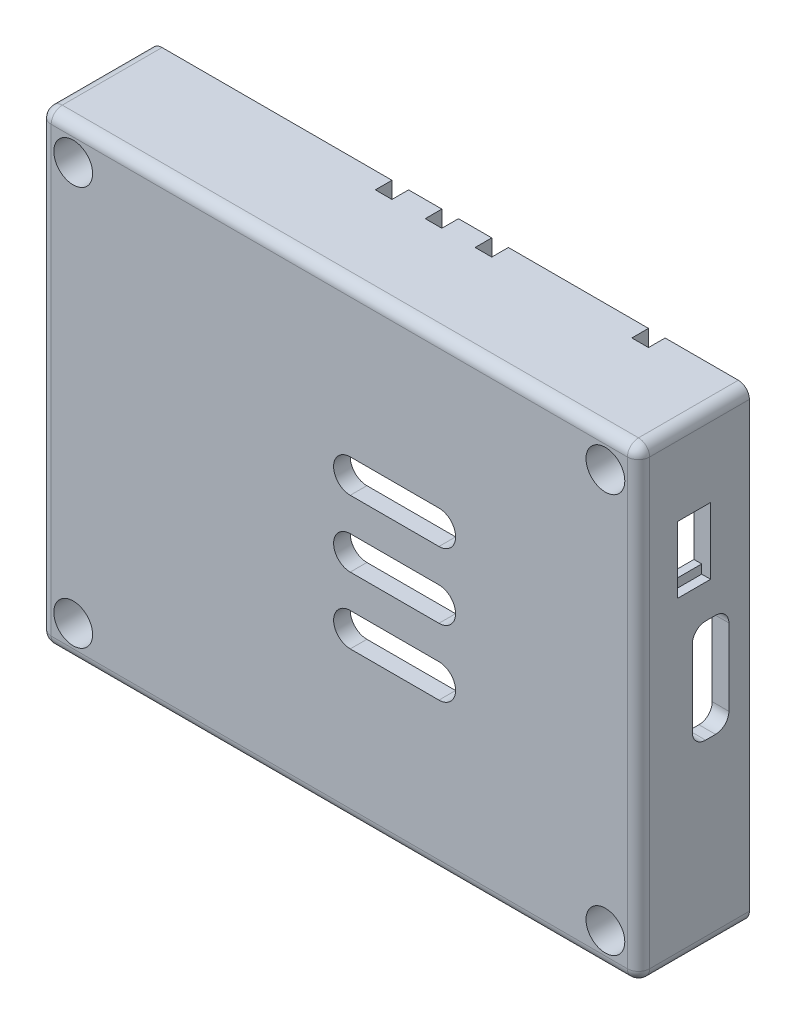
SolidWorks part; units mm, degrees
ref_plane "前视基准面" through (0, 0, 0) normal (0, 0, 1) x (1, 0, 0)
ref_plane "上视基准面" through (0, 0, 0) normal (0, 1, 0) x (1, 0, 0)
ref_plane "右视基准面" through (0, 0, 0) normal (1, 0, 0) x (0, 0, -1)
other "Configuration Table"
sketch "草图2" plane through (0, 0, 0) normal (0, 0, 1) x (1, 0, 0)
  line L32 (0.7633, 42.7757) -> (0.7633, 44.263) construction
  line L33 (0.7633, 44.263) -> (-41.2112, 44.263) construction
  line L34 (-41.2112, 44.263) -> (-41.2112, 42.7757) construction
  line L35 (-44.2239, 39.763) -> (-45.7112, 39.763) construction
  line L36 (-45.7112, 39.763) -> (-45.7112, 9.7885) construction
  line L37 (-45.7112, 9.7885) -> (-44.2239, 9.7885) construction
  line L38 (-41.2112, 6.7758) -> (-41.2112, 5.2885) construction
  line L39 (-41.2112, 5.2885) -> (0.7633, 5.2885) construction
  line L40 (0.7633, 5.2885) -> (0.7633, 6.7758) construction
  line L41 (3.776, 9.7885) -> (5.2633, 9.7885) construction
  line L42 (5.2633, 9.7885) -> (5.2633, 20.2756) construction
  line L43 (5.2633, 20.2756) -> (-0.4009, 20.283) construction
  line L44 (-0.4136, 20.2957) -> (-0.4136, 29.2557) construction
  line L45 (-0.4009, 29.2684) -> (5.2633, 29.2684) construction
  line L46 (5.2633, 29.2684) -> (5.2633, 39.763) construction
  line L47 (5.2633, 39.763) -> (3.776, 39.763) construction
  circle A1 centre (-4.0239, 32.2757) radius 1.125 construction
  arc A12 (0.7633, 42.7757) -> (3.776, 39.763) centre (3.776, 42.7757) ccw construction
  arc A13 (-44.2239, 39.763) -> (-41.2112, 42.7757) centre (-44.2239, 42.7757) ccw construction
  arc A14 (-41.2112, 6.7758) -> (-44.2239, 9.7885) centre (-44.2239, 6.7758) ccw construction
  arc A15 (3.776, 9.7885) -> (0.7633, 6.7758) centre (3.776, 6.7758) ccw construction
  arc A16 (-0.4136, 20.2957) -> (-0.4009, 20.283) centre (-0.4009, 20.2957) ccw construction
  arc A17 (-0.4009, 29.2684) -> (-0.4136, 29.2557) centre (-0.4009, 29.2557) ccw construction
sketch "草图3" plane through (0, 0, 0) normal (0, 0, 1) x (1, 0, 0)
  line L1 (-47.2112, 45.763) -> (6.7633, 45.763)
  line L2 (-47.2112, 45.763) -> (-47.2112, 3.7885)
  line L3 (-47.2112, 3.7885) -> (6.7633, 3.7885)
  line L4 (6.7633, 45.763) -> (6.7633, 3.7885)
  line L6 (-45.7112, 39.763) -> (-45.7112, 9.7885) construction
  line L7 (0.7633, 44.263) -> (-41.2112, 44.263) construction
  point P4 (-20.2239, 45.763)
  point P7 (-20.2239, 44.263)
  point P11 (-47.2112, 24.7757)
  point P12 (-45.7112, 24.7757)
  dimension "D1" = 1.5
  dimension "D2" = 1.5
extrude "凸台-拉伸1" add sketch "草图3" along normal blind 10
sketch "草图4" plane through (0, 0, 0) normal (0, 0, 1) x (1, 0, 0)
  line L32 (0.7633, 42.7757) -> (0.7633, 44.263)
  line L33 (0.7633, 44.263) -> (-41.2112, 44.263)
  line L34 (-41.2112, 44.263) -> (-41.2112, 42.7757)
  line L35 (-44.2239, 39.763) -> (-45.7112, 39.763)
  line L36 (-45.7112, 39.763) -> (-45.7112, 9.7885)
  line L37 (-45.7112, 9.7885) -> (-44.2239, 9.7885)
  line L38 (-41.2112, 6.7758) -> (-41.2112, 5.2885)
  line L39 (-41.2112, 5.2885) -> (0.7633, 5.2885)
  line L40 (0.7633, 5.2885) -> (0.7633, 6.7758)
  line L41 (3.776, 9.7885) -> (5.2633, 9.7885)
  line L46 (5.2633, 9.7885) -> (5.2633, 39.763)
  line L47 (5.2633, 39.763) -> (3.776, 39.763)
  arc A12 (0.7633, 42.7757) -> (3.776, 39.763) centre (3.776, 42.7757) ccw
  arc A13 (-44.2239, 39.763) -> (-41.2112, 42.7757) centre (-44.2239, 42.7757) ccw
  arc A14 (-41.2112, 6.7758) -> (-44.2239, 9.7885) centre (-44.2239, 6.7758) ccw
  arc A15 (3.776, 9.7885) -> (0.7633, 6.7758) centre (3.776, 6.7758) ccw
  point P9 (5.2633, 20.0021)
  point P12 (5.5493, 9.7885)
  point P18 (0, 0)
extrude "切除-拉伸1" cut sketch "草图4" along normal blind 8.5
sketch "草图5" plane through (0, 0, 8.5) normal (0, 0, -1) x (-1, 0, 0)
  line L0 (45.7112, 39.763) -> (45.7112, 9.7885) construction
  line L1 (-6.7633, 3.7885) -> (-6.7633, 45.763) construction
  line L6 (15.2367, 20.2757) -> (15.2367, 29.2757) construction
  line L7 (6.7367, 20.2757) -> (6.7367, 29.2757)
  line L8 (23.7367, 20.2757) -> (23.7367, 29.2757)
  line L9 (15.2367, 20.2757) -> (15.2367, 29.2757) construction
  line L10 (7.4867, 20.2757) -> (7.4867, 29.2757)
  line L11 (22.9867, 20.2757) -> (22.9867, 29.2757)
  arc A0 (6.7367, 20.2757) -> (23.7367, 20.2757) centre (15.2367, 20.2757) ccw
  arc A1 (23.7367, 29.2757) -> (6.7367, 29.2757) centre (15.2367, 29.2757) ccw
  arc A2 (7.4867, 20.2757) -> (22.9867, 20.2757) centre (15.2367, 20.2757) ccw
  arc A3 (22.9867, 29.2757) -> (7.4867, 29.2757) centre (15.2367, 29.2757) ccw
  point P0 (0, 0)
  point P3 (45.7112, 24.7757)
  point P14 (15.2367, 24.7757)
  point P19 (15.2367, 11.7757)
  point P20 (15.2367, 37.7757)
  point P23 (15.2367, 24.7757)
  point P28 (15.2367, 12.5257)
  point P29 (15.2367, 37.0257)
  dimension "D1" = 17
  dimension "D2" = 26
  dimension "D3" = 24.5
  dimension "D4" = 15.5
  dimension "D5" = 22
extrude "凸台-拉伸2" add sketch "草图5" along normal blind 1
sketch "草图6" plane through (0, 0, 7.5) normal (0, 0, -1) x (-1, 0, 0)
  line L1 (6.7367, 28.7757) -> (12.7367, 28.7757)
  line L2 (6.7367, 28.7757) -> (6.7367, 20.7757)
  line L3 (6.7367, 20.7757) -> (12.7367, 20.7757)
  line L4 (23.7367, 28.7757) -> (23.7367, 20.7757)
  line L11 (6.7367, 29.2757) -> (6.7367, 20.2757) construction
  line L12 (23.7367, 20.2757) -> (23.7367, 29.2757) construction
  line L13 (7.4867, 29.2757) -> (7.4867, 20.2757) construction
  line L14 (15.2367, 28.7757) -> (15.2367, 20.7757) construction
  line L15 (17.7367, 39.4071) -> (12.7367, 39.4071)
  line L16 (17.7367, 39.4071) -> (17.7367, 28.7757)
  line L17 (17.7367, 10.1444) -> (12.7367, 10.1444)
  line L18 (12.7367, 39.4071) -> (12.7367, 28.7757)
  line L19 (12.7367, 20.7757) -> (12.7367, 10.1444)
  line L20 (17.7367, 28.7757) -> (23.7367, 28.7757)
  line L21 (17.7367, 20.7757) -> (17.7367, 10.1444)
  line L22 (17.7367, 20.7757) -> (23.7367, 20.7757)
  point P8 (7.4867, 24.7757)
  point P9 (23.7367, 24.7757)
  point P21 (15.2367, 39.4071)
  dimension "D1" = 8
  dimension "D2" = 5
extrude "切除-拉伸6" cut sketch "草图6" against normal up to surface (1 mm away) up to face at (-15.2367, 24.7757, 8.5)
sketch "草图7" plane through (0, 0, 8.5) normal (0, 0, -1) x (-1, 0, 0)
  line L0 (45.7112, 39.763) -> (45.7112, 9.7885) construction
  line L2 (12.7367, 36.6114) -> (17.7367, 12.94) construction
  line L3 (11.2367, 24.7757) -> (19.2367, 24.7757) construction
  line L4 (11.2367, 26.2757) -> (19.2367, 26.2757)
  line L5 (11.2367, 23.2757) -> (19.2367, 23.2757)
  line L6 (11.2367, 18.7757) -> (19.2367, 18.7757) construction
  line L7 (11.2367, 20.2757) -> (19.2367, 20.2757)
  line L8 (11.2367, 17.2757) -> (19.2367, 17.2757)
  line L10 (15.2367, 24.7757) -> (15.2367, 36.6114) construction
  line L13 (17.7367, 36.6114) -> (12.7367, 12.94) construction
  line L14 (6.7535, 24.7757) -> (27.8266, 24.7757) construction
  line L15 (11.2367, 30.7757) -> (19.2367, 30.7757) construction
  line L16 (11.2367, 29.2757) -> (19.2367, 29.2757)
  line L17 (11.2367, 32.2757) -> (19.2367, 32.2757)
  arc A0 (11.2367, 26.2757) -> (11.2367, 23.2757) centre (11.2367, 24.7757) ccw
  arc A1 (19.2367, 23.2757) -> (19.2367, 26.2757) centre (19.2367, 24.7757) ccw
  arc A2 (11.2367, 20.2757) -> (11.2367, 17.2757) centre (11.2367, 18.7757) ccw
  arc A3 (19.2367, 17.2757) -> (19.2367, 20.2757) centre (19.2367, 18.7757) ccw
  arc A6 (11.2367, 29.2757) -> (11.2367, 32.2757) centre (11.2367, 30.7757) cw
  arc A7 (19.2367, 32.2757) -> (19.2367, 29.2757) centre (19.2367, 30.7757) cw
  point P3 (45.7112, 24.7757)
  point P8 (15.2367, 24.7757)
  point P14 (15.2367, 18.7757)
  point P27 (15.2367, 30.7757)
  dimension "D1" = 8
  dimension "D2" = 1.5
  dimension "D3" = 6
extrude "切除-拉伸7" cut sketch "草图7" against normal up to surface (1.5 mm away) up to face at (-20.2239, 24.7757, 10)
sketch "草图8" plane through (0, 0, 8.5) normal (0, 0, -1) x (-1, 0, 0)
  line L0 (-5.2633, 9.7885) -> (-5.2633, 20.2756) construction
  line L1 (-3.776, 9.7885) -> (-5.2633, 9.7885)
  line L2 (-3.776, 9.7885) -> (-3.776, 11.7885)
  line L3 (-3.776, 11.7885) -> (-5.2633, 11.7885)
  line L4 (-5.2633, 9.7885) -> (-5.2633, 11.7885)
  line L5 (45.7112, 39.763) -> (45.7112, 9.7885) construction
  line L6 (44.2239, 9.7885) -> (45.7112, 9.7885)
  line L7 (44.2239, 9.7885) -> (44.2239, 11.7885)
  line L8 (44.2239, 11.7885) -> (45.7112, 11.7885)
  line L9 (45.7112, 9.7885) -> (45.7112, 11.7885)
  line L11 (44.2239, 39.763) -> (45.7112, 39.763)
  line L12 (44.2239, 39.763) -> (44.2239, 37.763)
  line L13 (44.2239, 37.763) -> (45.7112, 37.763)
  line L14 (45.7112, 39.763) -> (45.7112, 37.763)
  circle A0 centre (4.0239, 32.2757) radius 0.625
  circle A1 centre (4.0239, 32.2757) radius 2.25
  dimension "D1" = 1.25
  dimension "D2" = 4.5
  dimension "D3" = 2
  dimension "D4" = 2
  dimension "D5" = 2
extrude "凸台-拉伸3" add sketch "草图8" along normal blind 5
sketch "草图9" plane through (0, 0, 10) normal (0, 0, 1) x (1, 0, 0)
  line L0 (-20.2239, 45.763) -> (-20.2239, 3.7885) construction
  line L1 (6.7633, 45.763) -> (-47.2112, 45.763) construction
  line L2 (-47.2112, 3.7885) -> (6.7633, 3.7885) construction
  line L4 (-47.2112, 45.763) -> (-47.2112, 3.7885) construction
  line L5 (-47.2112, 24.7757) -> (6.7633, 24.7757) construction
  line L6 (6.7633, 3.7885) -> (6.7633, 45.763) construction
  circle A4 centre (-44.2239, 42.7757) radius 0.9
  circle A5 centre (3.776, 42.7757) radius 0.9
  circle A6 centre (3.776, 6.7758) radius 0.9
  circle A7 centre (-44.2239, 6.7758) radius 0.9
  dimension "D1" = 1.8
extrude "切除-拉伸8" cut sketch "草图9" against normal through all
sketch "草图10" plane through (0, 0, 10) normal (0, 0, 1) x (1, 0, 0)
  circle A0 centre (-44.2239, 42.7757) radius 1.75
  circle A1 centre (3.776, 42.7757) radius 1.75
  circle A2 centre (3.776, 6.7758) radius 1.75
  circle A3 centre (-44.2239, 6.7758) radius 1.75
  dimension "D1" = 3.5
  dimension "D2" = 3.5
  dimension "D3" = 3.5
  dimension "D4" = 3.5
extrude "切除-拉伸9" cut sketch "草图10" against normal offset from surface (8.8 mm away) 1.2 up to face at (-45.1239, 6.7758, 0)
sketch "草图11" plane through (0, 0, 0) normal (0, 0, -1) x (-1, 0, 0)
  line L0 (-0.7633, 44.263) -> (41.2112, 44.263) construction
  line L1 (0.8367, 44.263) -> (2.3367, 44.263)
  line L2 (0.8367, 44.263) -> (0.8367, 45.763)
  line L3 (0.8367, 45.763) -> (2.3367, 45.763)
  line L4 (2.3367, 44.263) -> (2.3367, 45.763)
  line L5 (-6.7633, 45.763) -> (47.2112, 45.763) construction
  line L6 (-6.7633, 3.7885) -> (-6.7633, 45.763) construction
  dimension "D1" = 1.5
  dimension "D2" = 7.6
extrude "切除-拉伸10" cut sketch "草图11" against normal blind 1.5
sketch "草图12" plane through (0, 0, 0) normal (0, 0, -1) x (-1, 0, 0)
  line L5 (-6.7633, 3.7885) -> (-6.7633, 45.763) construction
  line L8 (-6.7633, 29.2757) -> (-5.2633, 29.2757)
  line L9 (-6.7633, 29.2757) -> (-6.7633, 20.2757)
  line L10 (-6.7633, 20.2757) -> (-5.2633, 20.2757)
  line L11 (-5.2633, 29.2757) -> (-5.2633, 20.2757)
  line L12 (-5.2633, 9.7885) -> (-5.2633, 20.2756) construction
  line L13 (47.2112, 45.763) -> (47.2112, 3.7885) construction
  point P10 (47.2112, 24.7757)
  point P11 (-6.7633, 24.7757)
  dimension "D1" = 9
sketch "草图13" plane through (6.7633, 0, 0) normal (1, 0, 0) x (0, 0, -1)
  line L0 (-10, 3.7885) -> (-10, 45.763) construction
  line L1 (-5.15, 29.4257) -> (-1.85, 29.4257)
  line L2 (-5.15, 29.4257) -> (-5.15, 20.1257)
  line L3 (-5.15, 20.1257) -> (-1.85, 20.1257)
  line L4 (-1.85, 29.4257) -> (-1.85, 20.1257)
  line L5 (0, 39.763) -> (0, 9.7885) construction
  point P6 (-10, 24.7757)
  point P7 (-1.85, 24.7757)
  dimension "D1" = 5.15
  dimension "D2" = 3.3
  dimension "D3" = 9.3
extrude "切除-拉伸16" cut sketch "草图13" against normal up to surface (1.5 mm away) up to face at (5.2633, 20.4466, 4)
fillet "圆角2" radius 1.2 4 edges at (6.0133, 20.1257, 5.15) (6.0133, 29.4257, 1.85) (6.0133, 29.4257, 5.15) (6.0133, 20.1257, 1.85)
sketch "草图14" plane through (0, 0, 0) normal (0, 0, -1) x (-1, 0, 0)
  line L0 (45.7112, 39.763) -> (45.7112, 9.7885) construction
  line L1 (45.7112, 19.7757) -> (47.2112, 19.7757)
  line L2 (45.7112, 19.7757) -> (45.7112, 29.7757)
  line L3 (45.7112, 29.7757) -> (47.2112, 29.7757)
  line L4 (47.2112, 19.7757) -> (47.2112, 29.7757)
  line L5 (47.2112, 45.763) -> (47.2112, 3.7885) construction
  point P8 (47.2112, 24.7757)
  point P9 (47.2112, 24.7757)
  dimension "D1" = 10
extrude "切除-拉伸17" cut sketch "草图14" against normal blind 1.8
sketch "草图15" plane through (6.7633, 0, 0) normal (1, 0, 0) x (0, 0, -1)
  line L0 (0, 42.7757) -> (0, 39.763) construction
  line L1 (-6.5, 38.463) -> (-3.5, 38.463)
  line L2 (-6.5, 38.463) -> (-6.5, 32.463)
  line L3 (-6.5, 32.463) -> (-3.5, 32.463)
  line L4 (-3.5, 38.463) -> (-3.5, 32.463)
  line L5 (-6.5, 35.463) -> (-3.5, 35.463) construction
  line L6 (-10, 45.763) -> (0, 45.763) construction
  dimension "D1" = 3
  dimension "D2" = 6
  dimension "D3" = 6.5
  dimension "D4" = 10.3
extrude "切除-拉伸18" cut sketch "草图15" against normal blind 0.8
sketch "草图16" plane through (5.9633, 0, 0) normal (1, 0, 0) x (0, 0, -1)
  line L0 (-6.5, 38.463) -> (-6.5, 32.463) construction
  line L1 (-6.5, 33.263) -> (-3.5, 33.263)
  line L2 (-6.5, 33.263) -> (-6.5, 37.663)
  line L3 (-6.5, 37.663) -> (-3.5, 37.663)
  line L4 (-3.5, 33.263) -> (-3.5, 37.663)
  line L5 (-3.5, 32.463) -> (-3.5, 38.463) construction
  point P8 (-3.5, 35.463)
  point P9 (-3.5, 35.463)
  dimension "D1" = 4.4
extrude "切除-拉伸19" cut sketch "草图16" against normal up to surface (0.7 mm away) up to face at (5.2633, 24.7757, 3.5)
chamfer "倒角1" distance 1.6 distance2 5 1 edges at (-1.7739, 32.2757, 8.5) first distance on face at (-21.9058, 17.5607, 8.5)
fillet "圆角4" radius 1 8 edges at (-47.2112, 45.763, 5) (-47.2112, 24.7757, 10) (-47.2112, 3.7885, 5) (6.7633, 3.7885, 5) (-20.2239, 3.7885, 10) (6.7633, 24.7757, 10) (6.7633, 45.763, 5) (-20.2239, 45.763, 10)
sketch "草图17" plane through (0, 0, 0) normal (0, 0, -1) x (-1, 0, 0)
  line L1 (19.474, 3.4743) -> (20.974, 3.4743)
  line L2 (19.474, 3.4743) -> (19.474, 5.4771)
  line L3 (19.474, 5.4771) -> (20.974, 5.4771)
  line L4 (20.974, 3.4743) -> (20.974, 5.4771)
  line L5 (41.2112, 5.2885) -> (-0.7633, 5.2885) construction
  line L6 (-6.7633, 24.7757) -> (47.2112, 24.7757) construction
  line L7 (-6.7633, 29.2757) -> (-6.7633, 20.2757) construction
  line L8 (47.2112, 19.7757) -> (47.2112, 29.7757) construction
  line L9 (14.974, 5.5028) -> (14.974, 3.5773)
  line L10 (20.224, 5.4771) -> (20.2239, 44.263) construction
  line L11 (-0.7633, 44.263) -> (41.2112, 44.263) construction
  line L12 (23.974, 5.5028) -> (25.474, 5.5028)
  line L13 (23.974, 5.5028) -> (23.974, 3.5773)
  line L14 (23.974, 3.5773) -> (25.474, 3.5773)
  line L15 (25.474, 5.5028) -> (25.474, 3.5773)
  line L16 (16.474, 3.5773) -> (14.974, 3.5773)
  line L17 (16.474, 5.5028) -> (16.474, 3.5773)
  line L18 (16.474, 5.5028) -> (14.974, 5.5028)
  line L19 (16.474, 44.0486) -> (14.974, 44.0486)
  line L20 (16.474, 44.0486) -> (16.474, 45.9742)
  line L21 (16.474, 45.9742) -> (14.974, 45.9742)
  line L22 (25.474, 44.0486) -> (25.474, 45.9742)
  line L23 (23.974, 45.9742) -> (25.474, 45.9742)
  line L24 (23.974, 44.0486) -> (23.974, 45.9742)
  line L25 (23.974, 44.0486) -> (25.474, 44.0486)
  line L26 (14.974, 44.0486) -> (14.974, 45.9742)
  line L27 (20.974, 46.0772) -> (20.974, 44.0744)
  line L28 (19.474, 44.0744) -> (20.974, 44.0744)
  line L29 (19.474, 46.0772) -> (19.474, 44.0744)
  line L30 (19.474, 46.0772) -> (20.974, 46.0772)
  point P8 (20.224, 5.2885)
  point P9 (20.224, 3.4743)
  dimension "D1" = 1.5
  dimension "D2" = 1.5
  dimension "D3" = 3
extrude "切除-拉伸20" cut sketch "草图17" against normal blind 1.5
